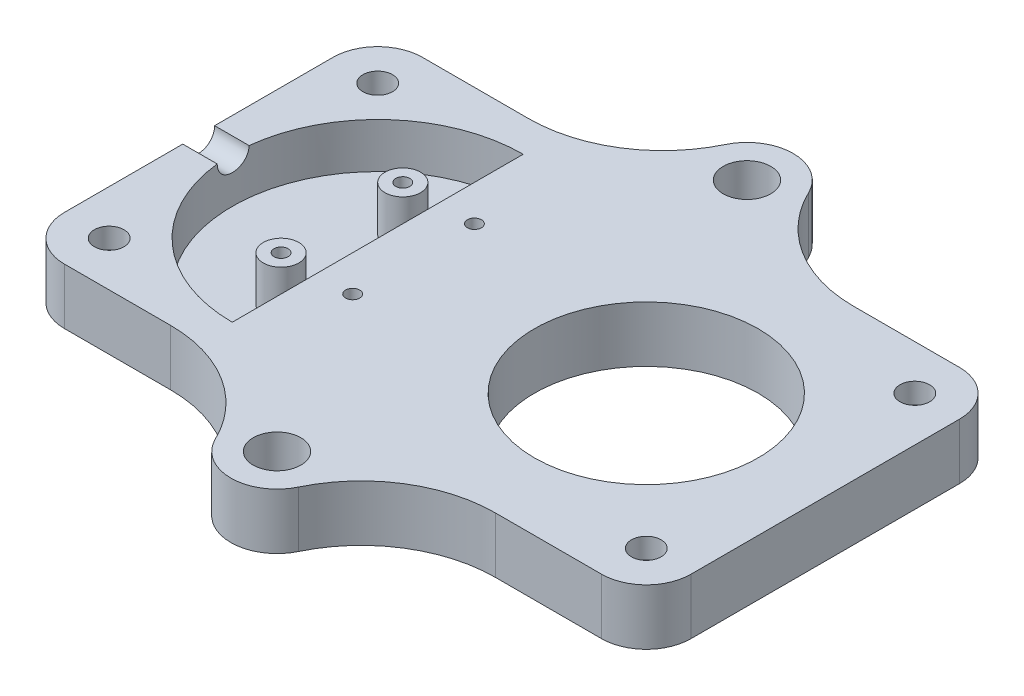
SolidWorks part; units mm, degrees
ref_plane "Front Plane" through (0, 0, 0) normal (0, 0, 1) x (1, 0, 0)
ref_plane "Top Plane" through (0, 0, 0) normal (0, 1, 0) x (1, 0, 0)
ref_plane "Right Plane" through (0, 0, 0) normal (1, 0, 0) x (0, 0, -1)
sketch "Sketch1" plane through (0, 0, 0) normal (0, 1, 0) x (1, 0, 0)
  line L0 (38.1, 19.05) -> (38.1, 25.4) construction
  line L1 (-19.05, -25.4) -> (57.15, -25.4)
  line L2 (-25.4, -19.05) -> (-25.4, 19.05)
  line L3 (-19.05, 25.4) -> (57.15, 25.4)
  line L4 (63.5, -19.05) -> (63.5, 19.05)
  line L5 (-25.4, -25.4) -> (63.5, 25.4) construction
  line L6 (-25.4, 25.4) -> (63.5, -25.4) construction
  line L7 (57.15, 0) -> (63.5, 0) construction
  line L9 (-7.62, -11.176) -> (7.62, -11.176) construction
  line L10 (-7.62, -11.176) -> (-7.62, 11.176) construction
  line L11 (-7.62, 11.176) -> (7.62, 11.176) construction
  line L12 (7.62, -11.176) -> (7.62, 11.176) construction
  line L13 (-7.62, -11.176) -> (7.62, 11.176) construction
  line L14 (-7.62, 11.176) -> (7.62, -11.176) construction
  circle A0 centre (0, 0) radius 19.05 construction
  circle A1 centre (38.1, 0) radius 19.05 construction
  circle A2 centre (38.1, 0) radius 12.7 construction
  circle A3 centre (38.1, 0) radius 15.875
  arc A4 (-25.4, 19.05) -> (-19.05, 25.4) centre (-19.05, 19.05) cw
  arc A5 (-19.05, -25.4) -> (-25.4, -19.05) centre (-19.05, -19.05) cw
  arc A6 (57.15, -25.4) -> (63.5, -19.05) centre (57.15, -19.05) ccw
  arc A7 (57.15, 25.4) -> (63.5, 19.05) centre (57.15, 19.05) cw
  circle A8 centre (-19.05, 19.05) radius 2.1
  circle A9 centre (-19.05, -19.05) radius 2.1
  circle A10 centre (57.15, -19.05) radius 2.1
  circle A11 centre (57.15, 19.05) radius 2.1
  point P6 (19.05, 0)
  dimension "D1" = 38.1
  dimension "D2" = 38.1
  dimension "D3" = 50.8
  dimension "D7" = 25.4
  dimension "D8" = 31.75
  dimension "D9" = 6.35
  dimension "D10" = 4.2
  dimension "D4" = 88.9
  dimension "D5" = 15.24
  dimension "D6" = 22.352
extrude "Boss-Extrude1" add sketch "Sketch1" along normal blind 7.9248
sketch "Sketch2" plane through (0, 7.9248, 0) normal (0, 1, 0) x (1, 0, 0)
  line L0 (0, 20.6375) -> (38.1, 20.6375)
  line L1 (38.1, -20.6375) -> (0, -20.6375)
  arc A0 (0, 20.6375) -> (0, -20.6375) centre (0, 0) ccw
  arc A1 (38.1, -20.6375) -> (38.1, 20.6375) centre (38.1, 0) ccw
  dimension "D1" = 41.275
extrude "Cut-Extrude1" cut sketch "Sketch2" against normal offset from surface (6.4008 mm away) 1.524 up to face at (57.15, 0, 21.15)
sketch "Sketch3" plane through (0, 1.524, 0) normal (0, 1, 0) x (1, 0, 0)
  line L0 (0, 0) -> (0, 50000) construction
  line L1 (-7.62, -11.176) -> (7.62, -11.176) construction
  line L2 (-7.62, -11.176) -> (-7.62, 11.176) construction
  line L3 (-7.62, 11.176) -> (7.62, 11.176) construction
  line L4 (7.62, -11.176) -> (7.62, 11.176) construction
  line L5 (-7.62, -11.176) -> (7.62, 11.176) construction
  line L6 (-7.62, 11.176) -> (7.62, -11.176) construction
  line L7 (0, 0) -> (50000, 0) construction
  circle A0 centre (5.08, 8.636) radius 0.997
  circle A1 centre (5.08, -8.636) radius 0.997
  circle A2 centre (-5.08, 8.636) radius 0.997
  circle A3 centre (-5.08, -8.636) radius 0.997
  circle A4 centre (-5.08, 8.636) radius 2.521
  circle A5 centre (5.08, 8.636) radius 2.521
  circle A6 centre (5.08, -8.636) radius 2.521
  circle A7 centre (-5.08, -8.636) radius 2.521
  point P0 (0, 0)
  dimension "D3" = 2.54
  dimension "D4" = 2.54
  dimension "D5" = 1.9939
  dimension "D6" = 1.524
  dimension "D1" = 22.352
  dimension "D2" = 15.24
extrude "Boss-Extrude2" add sketch "Sketch3" along normal up to surface (6.4008 mm away) up to face at (19.05, 7.9248, 0)
sketch "Sketch4" plane through (0, 1.524, 0) normal (0, 1, 0) x (1, 0, 0)
  circle A0 centre (-5.08, -8.636) radius 0.9969 construction
  circle A1 centre (5.08, -8.636) radius 0.9969
  circle A2 centre (5.08, -8.636) radius 0.997
  circle A3 centre (5.08, 8.636) radius 0.9969 construction
  circle A4 centre (-5.08, 8.636) radius 0.9969 construction
  circle A5 centre (-5.08, -8.636) radius 0.997
  circle A6 centre (5.08, 8.636) radius 0.997
  circle A7 centre (-5.08, 8.636) radius 0.997
  dimension "D1" = 0
extrude "Cut-Extrude2" cut sketch "Sketch4" against normal through all
sketch "Sketch5" plane through (0, 1.524, 0) normal (0, 1, 0) x (1, 0, 0)
  line L0 (0, 20.6375) -> (0, -20.6375)
  line L1 (38.1, 20.6375) -> (0, 20.6375) construction
  line L2 (0, -20.6375) -> (38.1, -20.6375) construction
  line L3 (38.1, 20.6375) -> (0, 20.6375)
  line L4 (0, -20.6375) -> (38.1, -20.6375)
  circle A0 centre (38.1, 0) radius 15.875 construction
  arc A1 (38.1, -20.6375) -> (38.1, 20.6375) centre (38.1, 0) ccw construction
  circle A2 centre (38.1, 0) radius 15.875
  arc A3 (38.1, -20.6375) -> (38.1, 20.6375) centre (38.1, 0) ccw
  circle A4 centre (5.08, -8.636) radius 0.9969 construction
  circle A5 centre (5.08, 8.636) radius 0.9969 construction
  circle A6 centre (5.08, -8.636) radius 0.997
  circle A7 centre (5.08, 8.636) radius 0.997
extrude "Boss-Extrude3" add sketch "Sketch5" along normal up to surface (6.4008 mm away) up to face at (19.05, 7.9248, 0)
sketch "Sketch6" plane through (0, 0, 0) normal (0, -1, 0) x (1, 0, 0)
  line L0 (38.1, 0) -> (0, 0) construction
  line L1 (19.05, 0) -> (19.05, 50000) construction
  line L2 (-19.05, 25.4) -> (57.15, 25.4) construction
  line L3 (42.1159, 25.4) -> (-4.0159, 25.4)
  line L4 (42.1159, -25.4) -> (-4.0159, -25.4)
  line L6 (22.2579, 38.8937) -> (15.8421, 38.8937) construction
  line L7 (15.8421, 38.8937) -> (12.6342, 33.3375) construction
  line L8 (12.6342, 33.3375) -> (15.8421, 27.7812) construction
  line L9 (15.8421, 27.7812) -> (22.2579, 27.7812) construction
  line L10 (22.2579, 27.7812) -> (25.4658, 33.3375) construction
  line L11 (25.4658, 33.3375) -> (22.2579, 38.8937) construction
  circle A0 centre (19.05, 33.3375) radius 3.3782
  arc A1 (42.1159, 25.4) -> (24.9538, 36.1818) centre (42.1159, 44.45) cw
  arc A2 (24.9538, 36.1818) -> (19.05, 39.8907) centre (19.05, 33.3375) ccw
  arc A3 (13.1462, 36.1818) -> (19.05, 39.8907) centre (19.05, 33.3375) cw
  arc A4 (-4.0159, 25.4) -> (13.1462, 36.1818) centre (-4.0159, 44.45) ccw
  arc A5 (-4.0159, -25.4) -> (13.1462, -36.1818) centre (-4.0159, -44.45) cw
  arc A6 (13.1462, -36.1818) -> (19.05, -39.8907) centre (19.05, -33.3375) ccw
  arc A7 (24.9538, -36.1818) -> (19.05, -39.8907) centre (19.05, -33.3375) cw
  arc A8 (42.1159, -25.4) -> (24.9538, -36.1818) centre (42.1159, -44.45) ccw
  circle A9 centre (19.05, -33.3375) radius 3.3782
  circle A10 centre (19.05, 33.3375) radius 6.4158 construction
  point P8 (19.05, 0)
  point P21 (19.05, 25.4)
  point P30 (19.05, -25.4)
  dimension "D1" = 6.7564
  dimension "D2" = 66.675
  dimension "D3" = 3.175
  dimension "D4" = 19.05
  dimension "D5" = 11.1125
extrude "Boss-Extrude4" add sketch "Sketch6" against normal up to surface (7.9248 mm away) up to face at (-10.3187, 7.9248, 0)
sketch "Sketch7" plane through (-25.4, 0, 0) normal (-1, 0, 0) x (0, 0, 1)
  line L0 (-19.05, 7.9248) -> (19.05, 7.9248) construction
  circle A0 centre (0, 7.9248) radius 2.2606
  dimension "D1" = 4.5212
extrude "Cut-Extrude3" cut sketch "Sketch7" against normal up to next
sketch "Sketch8" plane through (0, 0, 0) normal (0, -1, 0) x (1, 0, 0)
  line L1 (-17.0004, 22.6) -> (-21.0996, 22.6)
  line L2 (-21.0996, 22.6) -> (-23.1492, 19.05)
  line L3 (-23.1492, 19.05) -> (-21.0996, 15.5)
  line L4 (-21.0996, 15.5) -> (-17.0004, 15.5)
  line L5 (-17.0004, 15.5) -> (-14.9508, 19.05)
  line L6 (-14.9508, 19.05) -> (-17.0004, 22.6)
  line L7 (-17.0004, -15.5) -> (-21.0996, -15.5)
  line L8 (-21.0996, -15.5) -> (-23.1492, -19.05)
  line L9 (-23.1492, -19.05) -> (-21.0996, -22.6)
  line L10 (-21.0996, -22.6) -> (-17.0004, -22.6)
  line L11 (-17.0004, -22.6) -> (-14.9508, -19.05)
  line L12 (-14.9508, -19.05) -> (-17.0004, -15.5)
  line L13 (59.1996, -15.5) -> (55.1004, -15.5)
  line L14 (55.1004, -15.5) -> (53.0508, -19.05)
  line L15 (53.0508, -19.05) -> (55.1004, -22.6)
  line L16 (55.1004, -22.6) -> (59.1996, -22.6)
  line L17 (59.1996, -22.6) -> (61.2492, -19.05)
  line L18 (61.2492, -19.05) -> (59.1996, -15.5)
  line L19 (59.1996, 22.6) -> (55.1004, 22.6)
  line L20 (55.1004, 22.6) -> (53.0508, 19.05)
  line L21 (53.0508, 19.05) -> (55.1004, 15.5)
  line L22 (55.1004, 15.5) -> (59.1996, 15.5)
  line L23 (59.1996, 15.5) -> (61.2492, 19.05)
  line L24 (61.2492, 19.05) -> (59.1996, 22.6)
  circle A0 centre (-19.05, 19.05) radius 3.55 construction
  circle A1 centre (-19.05, -19.05) radius 3.55 construction
  circle A2 centre (57.15, -19.05) radius 3.55 construction
  circle A3 centre (57.15, 19.05) radius 3.55 construction
  dimension "D1" = 7.1
extrude "Cut-Extrude4" cut sketch "Sketch8" against normal blind 5
